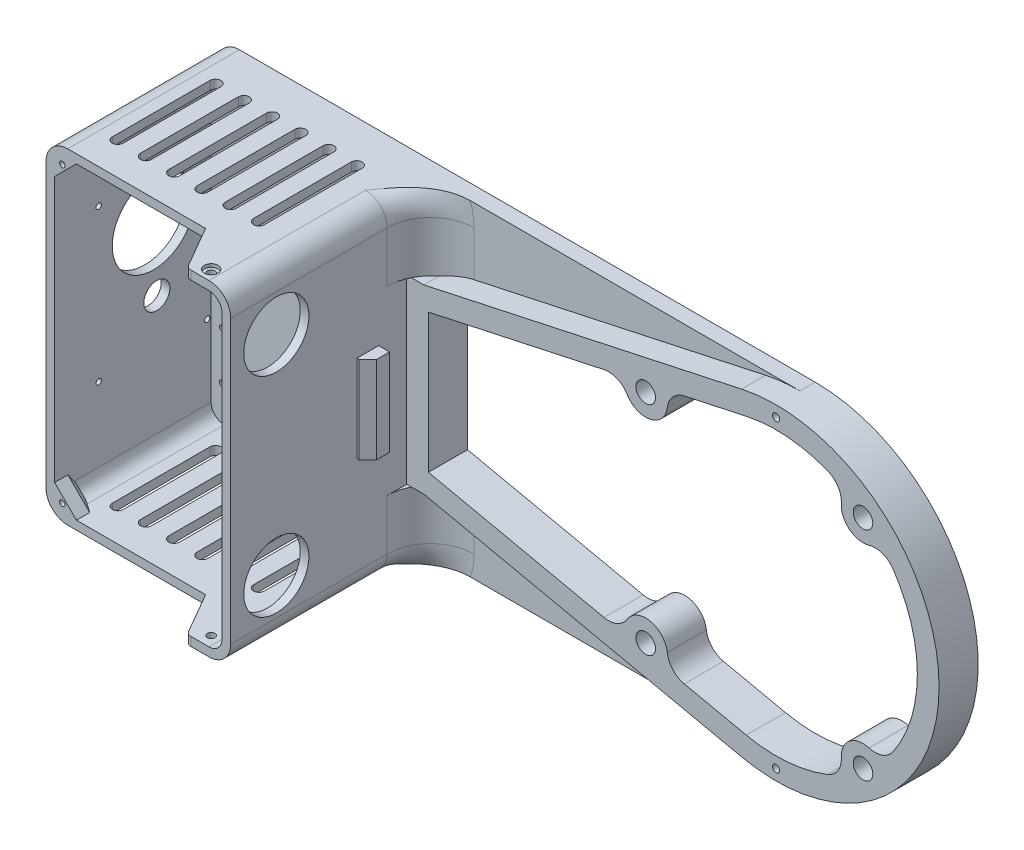
SolidWorks part; units mm, degrees
ref_plane "Front" through (0, 0, 0) normal (0, 0, 1) x (1, 0, 0)
ref_plane "Top" through (0, 0, 0) normal (0, 1, 0) x (1, 0, 0)
ref_plane "Right" through (0, 0, 0) normal (1, 0, 0) x (0, 0, -1)
sketch "Sketch1" plane through (47.5, -47.5, 0) normal (0, 0, 1) x (0, -1, 0)
  line L0 (-15.5701, -207.5) -> (1.8871, -126.7029)
  line L1 (-111.0339, -61.2273) -> (-104.8697, -89.757)
  line L2 (-79.4299, -207.5) -> (-15.5701, -207.5)
  line L3 (-96.8871, -126.7029) -> (-79.4299, -207.5)
  line L4 (-111.0339, -61.2273) -> (-79.4299, -207.5) construction
  line L5 (9.8697, -89.757) -> (16.0339, -61.2273)
  line L6 (-120.8084, -63.3392) -> (-89.2043, -209.6119)
  line L7 (-79.4299, -217.5) -> (-15.5701, -217.5)
  line L8 (-5.7957, -209.6119) -> (25.8084, -63.3392)
  line L9 (-15.5701, -207.5) -> (16.0339, -61.2273) construction
  line L10 (-97.5, -107.5) -> (-97.5, -7.5) construction
  line L11 (2.5, -107.5) -> (2.5, -7.5) construction
  line L12 (2.5, -7.5) -> (-97.5, -7.5) construction
  line L13 (-47.5, -47.5) -> (-47.5, -323.5722) construction
  line L14 (43.5196, -47.5) -> (-142.3518, -47.5) construction
  arc A0 (-108.033, -23.8196) -> (-111.0339, -61.2273) centre (-47.5, -47.5) ccw
  arc A1 (16.0339, -61.2273) -> (-111.0339, -61.2273) centre (-47.5, -47.5) ccw construction
  arc A2 (-11.1095, 6.3584) -> (-83.8905, 6.3584) centre (-47.5, -47.5) ccw
  arc A3 (16.0339, -61.2273) -> (13.033, -23.8196) centre (-47.5, -47.5) ccw
  arc A4 (-79.4299, -207.5) -> (-79.4299, -207.5) centre (-79.4299, -207.5) ccw
  arc A5 (-15.5701, -207.5) -> (-15.5701, -207.5) centre (-15.5701, -207.5) ccw
  arc A6 (-89.2043, -209.6119) -> (-79.4299, -217.5) centre (-79.4299, -207.5) ccw
  arc A7 (-15.5701, -217.5) -> (-5.7957, -209.6119) centre (-15.5701, -207.5) ccw
  arc A8 (25.8084, -63.3392) -> (-120.8084, -63.3392) centre (-47.5, -47.5) ccw
  arc A9 (-92.3063, -116.0455) -> (-96.2976, -97.5725) centre (-97.5, -107.5) ccw
  circle A10 centre (-97.5, -107.5) radius 4.5
  circle A11 centre (2.5, -107.5) radius 4.5
  circle A12 centre (2.5, -7.5) radius 4.5
  circle A13 centre (-97.5, -7.5) radius 4.5
  arc A14 (-98.1101, -17.4814) -> (-87.896, -4.7138) centre (-97.5, -7.5) ccw
  arc A15 (-7.104, -4.7138) -> (3.1101, -17.4814) centre (2.5, -7.5) ccw
  arc A16 (1.2976, -97.5725) -> (-2.6937, -116.0455) centre (2.5, -107.5) ccw
  arc A17 (1.8871, -126.7029) -> (-2.6937, -116.0455) centre (-7.8873, -124.591) ccw
  arc A18 (9.8697, -89.757) -> (1.2976, -97.5725) centre (0.0953, -87.6451) cw
  arc A19 (3.1101, -17.4814) -> (13.033, -23.8196) centre (3.7202, -27.4627) cw
  arc A20 (-7.104, -4.7138) -> (-11.1095, 6.3584) centre (-16.708, -1.9275) ccw
  arc A21 (-87.896, -4.7138) -> (-83.8905, 6.3584) centre (-78.292, -1.9275) cw
  arc A22 (-98.1101, -17.4814) -> (-108.033, -23.8196) centre (-98.7202, -27.4627) ccw
  arc A23 (-104.8697, -89.757) -> (-96.2976, -97.5725) centre (-95.0953, -87.6451) ccw
  arc A24 (-92.3063, -116.0455) -> (-96.8871, -126.7029) centre (-87.1127, -124.591) ccw
  circle A26 centre (-117.5, -47.5) radius 1.65
  circle A27 centre (22.5, -47.5) radius 1.65
  point P22 (-47.5, -47.5)
  dimension "D2" = 75
  dimension "D7" = 9
  dimension "D8" = 9
  dimension "D9" = 9
  dimension "D10" = 9
  dimension "D16" = 10
  dimension "D17" = 10
  dimension "D18" = 10
  dimension "D19" = 10
  dimension "D20" = 10
  dimension "D21" = 3.3
  dimension "D22" = 3.3
  dimension "D24" = 70
  dimension "D3" = 50
  dimension "D4" = 50
  dimension "D5" = 40
  dimension "D6" = 100
  dimension "D11" = 100
  dimension "D12" = 160
  dimension "D13" = 63.8597
  dimension "D14" = 12.192
  dimension "D15" = 12.192
  dimension "D23" = 70
  dimension "D1" = 10
extrude "Boss-Extrude1" add sketch "Sketch1" along normal blind 18
sketch "Sketch3" plane through (0, 0, 0) normal (0, 0, -1) x (-1, 0, 0)
  line L0 (0, 0) -> (261.4966, 0) construction
  line L2 (265, 75) -> (0, 75)
  line L3 (275, 65) -> (275, -65)
  line L4 (265, -75) -> (0, -75)
  line L5 (0, 75) -> (0, -75)
  line L6 (275, 75) -> (0, -75) construction
  line L7 (275, -75) -> (0, 75) construction
  line L9 (170, 31.9299) -> (170, -31.9299) construction
  arc A0 (265, -75) -> (275, -65) centre (265, -65) ccw
  arc A1 (275, 65) -> (265, 75) centre (265, 65) ccw
  point P3 (137.5, 0)
  point P18 (0, 70)
  dimension "D3" = 10
  dimension "D1" = 75
  dimension "D2" = 105
extrude "Boss-Extrude2" add sketch "Sketch3" against normal blind 7
sketch "Sketch4" plane through (0, 0, 7) normal (0, 0, 1) x (1, 0, 0)
  line L0 (0, 0) -> (-275, 0) construction
  line L1 (-275, -65) -> (-275, 65) construction
  line L2 (0, -11) -> (-275, -11) construction
  line L3 (0, 66.4999) -> (0, -66.4999) construction
  line L4 (0, 11) -> (-275, 11) construction
  line L5 (0, -33) -> (-275, -33) construction
  line L6 (0, 33) -> (-275, 33) construction
  line L7 (-88.9755, -55) -> (-260.4482, -55) construction
  line L8 (0, 55) -> (-275, 55) construction
  line L9 (0, 66.4999) -> (0, -66.4999) construction
  line L10 (-266, 75) -> (-266, -75) construction
  line L11 (-265, 75) -> (0, 75) construction
  line L12 (0, -75) -> (-265, -75) construction
  line L13 (-183, 75) -> (-183, -75) construction
  circle A0 centre (-266, 55) radius 1.2
  circle A1 centre (-266, 33) radius 1.2
  circle A2 centre (-266, 11) radius 1.2
  circle A3 centre (-266, -11) radius 1.2
  circle A4 centre (-266, -33) radius 1.2
  circle A5 centre (-266, -55) radius 1.2
  circle A6 centre (-183, 55) radius 1.2
  circle A7 centre (-183, 33) radius 1.2
  circle A8 centre (-183, 11) radius 1.2
  circle A9 centre (-183, -11) radius 1.2
  circle A10 centre (-183, -33) radius 1.2
  circle A11 centre (-183, -55) radius 1.2
  dimension "D8" = 2.4
  dimension "D9" = 2.4
  dimension "D10" = 2.4
  dimension "D11" = 2.4
  dimension "D12" = 2.4
  dimension "D13" = 2.4
  dimension "D14" = 83
  dimension "D15" = 2.4
  dimension "D16" = 2.4
  dimension "D17" = 2.4
  dimension "D18" = 2.4
  dimension "D19" = 2.4
  dimension "D20" = 2.4
  dimension "D1" = 11
  dimension "D2" = 11
  dimension "D3" = 22
  dimension "D4" = 22
  dimension "D5" = 22
  dimension "D6" = 22
  dimension "D7" = 9
extrude "Cut-Extrude1" cut sketch "Sketch4" against normal through all
sketch "Sketch5" plane through (0, 0, 7) normal (0, 0, 1) x (1, 0, 0)
  line L6 (-42.257, -57.3697) -> (-13.7273, -63.5339)
  line L7 (0, -65) -> (0, 65)
  line L8 (-13.7273, 63.5339) -> (-42.257, 57.3697)
  line L9 (-79.2029, 49.3871) -> (-160, 31.9299)
  line L10 (-160, 31.9299) -> (-160, -31.9299)
  line L11 (-160, -31.9299) -> (-79.2029, -49.3871)
  line L12 (-42.257, -57.3697) -> (-13.7273, -63.5339)
  line L14 (-13.7273, 63.5339) -> (-42.257, 57.3697)
  line L15 (-79.2029, 49.3871) -> (-160, 31.9299)
  line L16 (-160, 31.9299) -> (-160, -31.9299)
  line L17 (-160, -31.9299) -> (-79.2029, -49.3871)
  line L18 (0, -65) -> (0, 65)
  circle A0 centre (-60, 50) radius 4.5 construction
  circle A1 centre (-60, -50) radius 4.5 construction
  circle A2 centre (-60, 50) radius 4.5
  circle A3 centre (-60, -50) radius 4.5
  arc A6 (-50.0725, -48.7976) -> (-42.257, -57.3697) centre (-40.1451, -47.5953) ccw
  arc A7 (-42.257, 57.3697) -> (-50.0725, 48.7976) centre (-40.1451, 47.5953) ccw
  arc A8 (-68.5455, 44.8063) -> (-50.0725, 48.7976) centre (-60, 50) ccw
  arc A9 (-68.5455, 44.8063) -> (-79.2029, 49.3871) centre (-77.091, 39.6127) ccw
  arc A10 (-79.2029, -49.3871) -> (-68.5455, -44.8063) centre (-77.091, -39.6127) ccw
  arc A11 (-50.0725, -48.7976) -> (-68.5455, -44.8063) centre (-60, -50) ccw
  arc A12 (-50.0725, -48.7976) -> (-42.257, -57.3697) centre (-40.1451, -47.5953) ccw
  arc A13 (-42.257, 57.3697) -> (-50.0725, 48.7976) centre (-40.1451, 47.5953) ccw
  arc A14 (-68.5455, 44.8063) -> (-50.0725, 48.7976) centre (-60, 50) ccw
  arc A15 (-68.5455, 44.8063) -> (-79.2029, 49.3871) centre (-77.091, 39.6127) ccw
  arc A16 (-79.2029, -49.3871) -> (-68.5455, -44.8063) centre (-77.091, -39.6127) ccw
  arc A17 (-50.0725, -48.7976) -> (-68.5455, -44.8063) centre (-60, -50) ccw
  arc A24 (-13.7273, -63.5339) -> (0, -65) centre (0, 0) ccw
  arc A25 (-13.7273, -63.5339) -> (0, -65) centre (0, 0) ccw
  arc A26 (0, 65) -> (-13.7273, 63.5339) centre (0, 0) ccw
  arc A27 (0, 65) -> (-13.7273, 63.5339) centre (0, 0) ccw
  dimension "D1" = 0
extrude "Cut-Extrude2" cut sketch "Sketch5" against normal through all
sketch "Sketch6" plane through (0, 0, 7) normal (0, 0, 1) x (1, 0, 0)
  line L0 (0, -75) -> (-265, -75) construction
  line L1 (-222.5, 75) -> (-222.5, -75) construction
  line L2 (-275, 0) -> (-170, 0) construction
  line L4 (-265, 71) -> (-180, 71)
  line L5 (-271, 65) -> (-271, -65)
  line L6 (-162.1119, 41.7043) -> (-15.8392, 73.3084)
  line L7 (0, 75) -> (-265, 75)
  line L8 (-275, 65) -> (-275, -65)
  line L9 (-265, -75) -> (0, -75)
  line L10 (-15.8392, -73.3084) -> (-162.1119, -41.7043)
  line L11 (-170, -31.9299) -> (-170, 31.9299)
  line L13 (-180, 75) -> (-265, 75)
  line L14 (-275, 65) -> (-275, -65)
  line L15 (-265, -75) -> (-180, -75)
  line L17 (-170, -65) -> (-170, 65)
  line L18 (-265, -71) -> (-180, -71)
  line L19 (-174, 65) -> (-174, -65)
  line L20 (-271, 71) -> (-174, -71) construction
  line L21 (-271, -71) -> (-174, 71) construction
  arc A0 (-180, -75) -> (-170, -65) centre (-180, -65) ccw
  arc A1 (-170, 65) -> (-180, 75) centre (-180, 65) ccw
  arc A2 (-180, 71) -> (-174, 65) centre (-180, 65) cw
  arc A3 (-174, -65) -> (-180, -71) centre (-180, -65) cw
  arc A4 (-162.1119, 41.7043) -> (-170, 31.9299) centre (-160, 31.9299) ccw
  arc A5 (-265, 75) -> (-275, 65) centre (-265, 65) ccw
  arc A6 (-275, -65) -> (-265, -75) centre (-265, -65) ccw
  arc A7 (-170, -31.9299) -> (-162.1119, -41.7043) centre (-160, -31.9299) ccw
  arc A9 (-265, 75) -> (-275, 65) centre (-265, 65) ccw
  arc A10 (-275, -65) -> (-265, -75) centre (-265, -65) ccw
  arc A12 (-265, -71) -> (-271, -65) centre (-265, -65) cw
  arc A13 (-265, 71) -> (-271, 65) centre (-265, 65) ccw
  arc A20 (-15.8392, -73.3084) -> (0, -75) centre (0, 0) ccw
  arc A22 (0, 75) -> (-15.8392, 73.3084) centre (0, 0) ccw
  point P21 (-170, -75)
  point P27 (-222.5, 0)
  dimension "D2" = 10
  dimension "D7" = 6
  dimension "D3" = 4
  dimension "D4" = 4
  dimension "D5" = 4
  dimension "D6" = 4
  dimension "D1" = 0
extrude "Boss-Extrude3" add sketch "Sketch6" along normal blind 92
sketch "Sketch7" plane through (-170, 0, 0) normal (1, 0, 0) x (0, 0, -1)
  line L0 (-18, 31.9299) -> (-18, -31.9299) construction
  line L1 (0, 0) -> (-140.0795, 0) construction
  circle A0 centre (-78, 48) radius 15
  circle A1 centre (-78, -48) radius 15
  dimension "D1" = 30
  dimension "D3" = 48
  dimension "D2" = 60
  dimension "D4" = 48
extrude "Cut-Extrude3" cut sketch "Sketch7" against normal up to next
sketch "Sketch8" plane through (0, -75, 0) normal (0, -1, 0) x (1, 0, 0)
  line L1 (-265, 99) -> (-180, 99) construction
  line L2 (-201.547, 79) -> (-275, 79)
  line L3 (-275, 99) -> (-275, 0) construction
  line L4 (-275, 79) -> (-275, 99)
  line L5 (-275, 99) -> (-190, 99)
  line L8 (-201.547, 79) -> (-190, 99)
  line L9 (-170, 99) -> (-170, 7) construction
  dimension "D1" = 60
  dimension "D2" = 20
  dimension "D3" = 20
  dimension "D4" = 85
extrude "Cut-Extrude4" cut sketch "Sketch8" against normal through all
sketch "Sketch10" plane through (0, 0, 0) normal (0, 1, 0) x (1, 0, 0)
  line L0 (-257, -64) -> (-257, -19) construction
  line L1 (-259.5, -64) -> (-259.5, -19)
  line L2 (-254.5, -64) -> (-254.5, -19)
  line L3 (-265, -79) -> (-265, 0) construction
  line L4 (-265, -79) -> (-201.547, -79) construction
  line L5 (-244, -64) -> (-244, -19) construction
  line L6 (-246.5, -64) -> (-246.5, -19)
  line L7 (-241.5, -64) -> (-241.5, -19)
  line L8 (-231, -64) -> (-231, -19) construction
  line L9 (-233.5, -64) -> (-233.5, -19)
  line L10 (-228.5, -64) -> (-228.5, -19)
  line L11 (-218, -64) -> (-218, -19) construction
  line L12 (-220.5, -64) -> (-220.5, -19)
  line L13 (-215.5, -64) -> (-215.5, -19)
  line L14 (-205, -64) -> (-205, -19) construction
  line L15 (-207.5, -64) -> (-207.5, -19)
  line L16 (-202.5, -64) -> (-202.5, -19)
  line L17 (-192, -64) -> (-192, -19) construction
  line L18 (-194.5, -64) -> (-194.5, -19)
  line L19 (-189.5, -64) -> (-189.5, -19)
  arc A0 (-259.5, -64) -> (-254.5, -64) centre (-257, -64) ccw
  arc A1 (-254.5, -19) -> (-259.5, -19) centre (-257, -19) ccw
  arc A2 (-246.5, -64) -> (-241.5, -64) centre (-244, -64) ccw
  arc A3 (-241.5, -19) -> (-246.5, -19) centre (-244, -19) ccw
  arc A4 (-233.5, -64) -> (-228.5, -64) centre (-231, -64) ccw
  arc A5 (-228.5, -19) -> (-233.5, -19) centre (-231, -19) ccw
  arc A6 (-220.5, -64) -> (-215.5, -64) centre (-218, -64) ccw
  arc A7 (-215.5, -19) -> (-220.5, -19) centre (-218, -19) ccw
  arc A8 (-207.5, -64) -> (-202.5, -64) centre (-205, -64) ccw
  arc A9 (-202.5, -19) -> (-207.5, -19) centre (-205, -19) ccw
  arc A10 (-194.5, -64) -> (-189.5, -64) centre (-192, -64) ccw
  arc A11 (-189.5, -19) -> (-194.5, -19) centre (-192, -19) ccw
  point P2 (-257, -41.5)
  point P15 (-244, -41.5)
  point P22 (-231, -41.5)
  point P29 (-218, -41.5)
  point P36 (-205, -41.5)
  point P43 (-192, -41.5)
  dimension "D4" = 15
  dimension "D1" = 45
  dimension "D2" = 8
  dimension "D3" = 5
  dimension "D5" = 6
extrude "Cut-Extrude6" cut sketch "Sketch10" against normal through all both and the other way through all
sketch "Sketch11" plane through (0, 0, 18) normal (0, 0, 1) x (1, 0, 0)
  line L0 (-162.1119, 41.7043) -> (-170, 41.7043)
  line L1 (-170, 31.9299) -> (-170, 65) construction
  line L2 (-170, 41.7043) -> (-170, 31.9299)
  line L4 (0, 0) -> (-275, 0) construction
  line L6 (-275, 65) -> (-275, -65) construction
  line L7 (-170, -41.7043) -> (-170, -31.9299)
  line L8 (-162.1119, -41.7043) -> (-170, -41.7043)
  arc A0 (-162.1119, 41.7043) -> (-170, 31.9299) centre (-160, 31.9299) ccw construction
  arc A1 (-162.1119, 41.7043) -> (-170, 31.9299) centre (-160, 31.9299) ccw
  arc A2 (-162.1119, -41.7043) -> (-170, -31.9299) centre (-160, -31.9299) cw
extrude "Boss-Extrude4" add sketch "Sketch11" against normal up to surface (11 mm away) up to face at (-116.2752, -60.9714, 7)
fillet "Fillet1" radius 20 3 edges at (-172.9289, 72.0711, 7) (-172.9289, -72.0711, 7) (-170, -53.3522, 7)
sketch "Sketch12" plane through (-170, 0, 0) normal (1, 0, 0) x (0, 0, -1)
  line L0 (-18, 75) -> (-18, -75) construction
  line L1 (-29.3941, 41.7043) -> (-18, 41.7043)
  line L2 (-29.3941, 41.7043) -> (-29.3941, -41.7043)
  line L3 (-29.3941, -41.7043) -> (-18, -41.7043)
  line L4 (-18, 41.7043) -> (-18, -41.7043)
  line L5 (-18, 41.7043) -> (-11.0845, 41.7043) construction
  line L6 (-18, -41.7043) -> (-11.0845, -41.7043) construction
extrude "Cut-Extrude7" cut sketch "Sketch12" along normal blind 9.5
sketch "Sketch13" plane through (0, 0, 79) normal (0, 0, 1) x (1, 0, 0)
  line L0 (-271, 61) -> (-261, 71)
  line L1 (-271, -65) -> (-271, 65) construction
  line L2 (-180, 71) -> (-265, 71) construction
  line L3 (-271, 65) -> (-271, -65) construction
  line L4 (-275, 65) -> (-275, -65) construction
  line L5 (-265, 71) -> (-201.547, 71) construction
  line L6 (-271, 61) -> (-271, 65)
  line L7 (-265, 71) -> (-261, 71)
  line L8 (-265, -71) -> (-180, -71) construction
  line L16 (0, 0) -> (-275, 0) construction
  line L20 (-271, -61) -> (-261, -71)
  line L21 (-261, -71) -> (-265, -71)
  line L22 (-271, -61) -> (-271, -65)
  arc A1 (-265, 71) -> (-271, 65) centre (-265, 65) ccw construction
  arc A2 (-265, 71) -> (-271, 65) centre (-265, 65) ccw
  arc A3 (-271, -65) -> (-265, -71) centre (-265, -65) ccw construction
  arc A4 (-271, -65) -> (-265, -71) centre (-265, -65) ccw
  dimension "D2" = 45
  dimension "D3" = 14
  dimension "D7" = 45
  dimension "D8" = 14
extrude "Boss-Extrude5" add sketch "Sketch13" against normal blind 10
sketch "Sketch14" plane through (0, 0, 79) normal (0, 0, 1) x (1, 0, 0)
  line L1 (-275, 65) -> (-275, -65) construction
  line L2 (-265, 75) -> (-201.547, 75) construction
  line L5 (-265, -75) -> (-201.547, -75) construction
  circle A0 centre (-267.5, 67.5) radius 1.25
  circle A3 centre (-267.5, -67.5) radius 1.25
  dimension "D1" = 2.5
  dimension "D2" = 7.5
  dimension "D3" = 2.5
  dimension "D6" = 7.5
  dimension "7" = 7.5
  dimension "D8" = 7.5
extrude "Cut-Extrude8" cut sketch "Sketch14" against normal blind 6
chamfer "Chamfer2" distance 3.9 angle 45 2 edges at (-266, -66, 69) (-266, 66, 69)
sketch "Sketch15" plane through (0, -71, 0) normal (0, 1, 0) x (1, 0, 0)
  line L0 (-180, -99) -> (-190, -99) construction
  line L1 (-170, -99) -> (-170, -27) construction
  circle A0 centre (-184, -94) radius 1.75
  point P0 (-184, -94)
  dimension "D3" = 3.5
  dimension "D1" = 5
  dimension "D2" = 14
extrude "Cut-Extrude9" cut sketch "Sketch15" against normal through all and the other way through all
sketch "Sketch16" plane through (0, -75, 0) normal (0, -1, 0) x (1, 0, 0)
  circle A0 centre (-184, 94) radius 3.15
  dimension "D1" = 6.3
extrude "Cut-Extrude10" cut sketch "Sketch16" against normal blind 1.5
sketch "Sketch17" plane through (0, 75, 0) normal (0, 1, 0) x (1, 0, 0)
  circle A0 centre (-184, -94) radius 3.15
  dimension "D1" = 6.3
extrude "Cut-Extrude11" cut sketch "Sketch17" against normal blind 1.5
fillet "Fillet2" radius 3 2 edges at (-190, 73, 99) (-190, -73, 99)
sketch "Sketch18" plane through (-170, 0, 0) normal (1, 0, 0) x (0, 0, -1)
  line L0 (0, 0) -> (-99, 0) construction
  line L1 (-99, -65) -> (-99, 65) construction
  line L2 (-18, 75) -> (-18, -75) construction
  line L3 (-40.9, 20) -> (-30.9, 20)
  line L4 (-40.9, 20) -> (-40.9, -20)
  line L5 (-40.9, -20) -> (-30.9, -20)
  line L6 (-30.9, 20) -> (-30.9, -20)
  line L7 (-40.9, 20) -> (-30.9, -20) construction
  line L8 (-40.9, -20) -> (-30.9, 20) construction
  point P5 (-35.9, 0)
  dimension "D1" = 12.9
  dimension "D2" = 40
  dimension "D3" = 10
extrude "Boss-Extrude6" add sketch "Sketch18" along normal blind 5
chamfer "Chamfer3" distance 4 angle 45 1 edges at (-165, 0, 40.9)
sketch "Sketch19" plane through (-275, 0, 0) normal (-1, 0, 0) x (0, 0, 1)
  line L0 (79, 65) -> (0, 65) construction
  line L3 (79, 65) -> (79, -65) construction
  circle A0 centre (33.5, 20) radius 19
  dimension "D1" = 38
  dimension "D2" = 45
  dimension "D3" = 45.5
extrude "Cut-Extrude12" cut sketch "Sketch19" against normal up to next
sketch "Sketch20" plane through (-275, 0, 0) normal (-1, 0, 0) x (0, 0, 1)
  line L0 (79, 65) -> (79, -65) construction
  line L1 (79, 75) -> (0, 75) construction
  circle A0 centre (8.75, -31) radius 1.25
  circle A1 centre (58.75, -31) radius 1.25
  circle A2 centre (8.75, 39) radius 1.25
  circle A3 centre (58.75, 39) radius 1.25
  point P0 (8.75, 39)
  point P1 (58.75, 39)
  point P3 (58.75, -31)
  point P5 (8.75, -31)
  dimension "D5" = 2.5
  dimension "D6" = 2.5
  dimension "D7" = 2.5
  dimension "D8" = 2.5
  dimension "D1" = 50
  dimension "D2" = 20.25
  dimension "D3" = 70
  dimension "D4" = 36
extrude "Cut-Extrude13" cut sketch "Sketch20" against normal up to next
sketch "Sketch21" plane through (-275, 0, 0) normal (-1, 0, 0) x (0, 0, 1)
  line L0 (0, -65) -> (0, 65) construction
  line L1 (79, 75) -> (0, 75) construction
  circle A0 centre (32, -10) radius 6
  dimension "D1" = 12
  dimension "D2" = 32
  dimension "D3" = 85
extrude "Cut-Extrude14" cut sketch "Sketch21" against normal up to next
